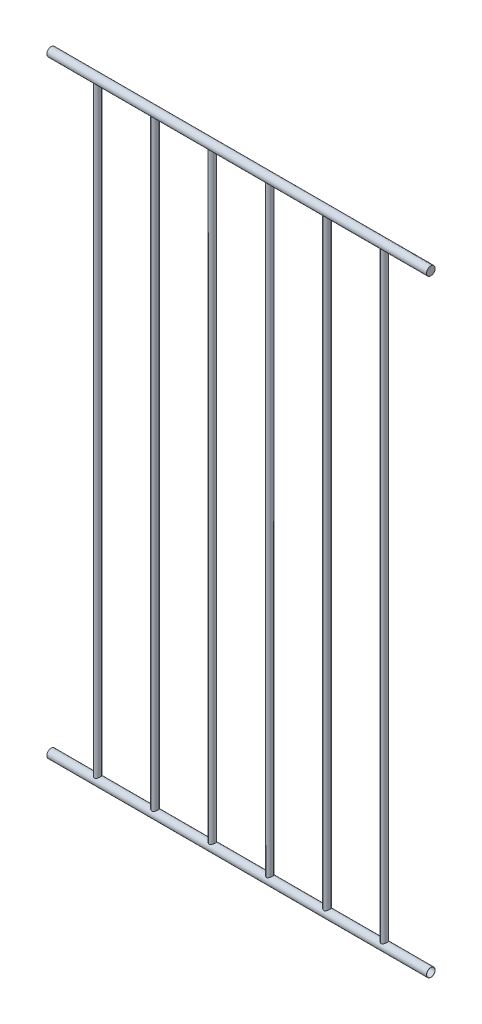
SolidWorks part; units mm, degrees
material "Copper"
ref_plane "Front Plane" through (0, 0, 0) normal (0, 0, 1) x (1, 0, 0)
ref_plane "Top Plane" through (0, 0, 0) normal (0, 1, 0) x (1, 0, 0)
ref_plane "Right Plane" through (0, 0, 0) normal (1, 0, 0) x (0, 0, -1)
sketch "Sketch1" plane through (0, 0, 0) normal (0, 0, 1) x (1, 0, 0)
  line L0 (0, 0) -> (1000, 0)
  line L1 (0, -1600) -> (1000, -1600)
  line L2 (122.5, 0) -> (122.5, -1600)
  line L3 (273.5, 0) -> (273.5, -1600)
  line L4 (424.5, 0) -> (424.5, -1600)
  line L5 (575.5, 0) -> (575.5, -1600)
  line L6 (726.5, 0) -> (726.5, -1600)
  line L7 (877.5, 0) -> (877.5, -1600)
  dimension "D1" = 1000
  dimension "D2" = 1000
  dimension "D3" = 1600
  dimension "D4" = 122.5
  dimension "D5" = 6
sketch "Sketch2" plane through (0, 0, 0) normal (1, 0, 0) x (0, 0, -1)
  line L0 (0, 0) -> (0, -1600) construction
  circle A0 centre (0, 0) radius 11.45
  circle A1 centre (0, -1600.0125) radius 11.45
  dimension "D1" = 22.9
  dimension "D3" = 22.9
extrude "Boss-Extrude1" add sketch "Sketch2" along normal blind 1000
sketch "Sketch3" plane through (0, 0, 0) normal (1, 0, 0) x (0, 0, -1)
  line L0 (0, 0) -> (0, -1600) construction
  circle A0 centre (0, 0) radius 11
  circle A1 centre (0, -1600) radius 11
  dimension "D1" = 22
  dimension "D2" = 22
extrude "Cut-Extrude1" cut sketch "Sketch3" along normal blind 1000
sketch "Sketch5" plane through (0, 0, 0) normal (0, 0, 1) x (1, 0, 0)
  line L0 (122.5, -800) -> (877.5, -800) construction
  line L1 (122.5, 0) -> (122.5, -1600) construction
  line L2 (877.5, 0) -> (877.5, -1600) construction
ref_plane "Plane2" through (0, -800, 0) normal (0, -1, 0) x (-1, 0, 0)
sketch "Sketch6" plane through (0, -800, 0) normal (0, -1, 0) x (-1, 0, 0)
  line L0 (0, 0) -> (-1000, 0) construction
  line L1 (-1000, 11.45) -> (-1000, -11.45) construction
  circle A0 centre (-122.5, 0) radius 8.0721
  circle A2 centre (-273.5, 0) radius 8.0721
  circle A3 centre (-424.5, 0) radius 8.0721
  circle A4 centre (-575.5, 0) radius 8.0721
  circle A5 centre (-726.5, 0) radius 8.0721
  circle A6 centre (-877.5, 0) radius 8.0721
  point P4 (-1000, 0)
  dimension "D1" = 122.5
  dimension "D2" = 122.5
extrude "Boss-Extrude3" add sketch "Sketch6" along normal up to surface and the other way up to surface up to face at (1000, -1600.0125, -11.45) other way up to face at (1000, 0, -11.45)
sketch "Sketch7" plane through (0, -800, 0) normal (0, -1, 0) x (-1, 0, 0)
  line L0 (0, 0) -> (-1000, 0) construction
  circle A0 centre (-122.5, 0) radius 7.5
  circle A1 centre (-273.5, 0) radius 7.5
  circle A2 centre (-424.5, 0) radius 7.5
  circle A3 centre (-575.5, 0) radius 7.5
  circle A4 centre (-726.5, 0) radius 7.5
  circle A5 centre (-877.5, 0) radius 7.5
  dimension "D1" = 15
  dimension "D2" = 122.5
extrude "Boss-Extrude4" add sketch "Sketch7" along normal up to surface and the other way up to surface up to face at (0, -1600.0125, -11.45) other way up to face at (1000, 0, -11.45)
sketch "Sketch8" plane through (0, 0, 0) normal (1, 0, 0) x (0, 0, -1)
  line L0 (0, 0) -> (0, -1600) construction
  circle A0 centre (0, -1600) radius 11
  circle A1 centre (0, 0) radius 11
extrude "Cut-Extrude2" cut sketch "Sketch8" along normal through all
sketch "Sketch9" plane through (0, -800, 0) normal (0, -1, 0) x (-1, 0, 0)
  line L0 (0, 0) -> (-1000, 0) construction
  line L1 (-1000, 11.45) -> (-1000, -11.45) construction
  circle A0 centre (-122.5, 0) radius 7.5
  circle A1 centre (-273.5, 0) radius 7.5
  circle A2 centre (-424.5, 0) radius 7.5
  circle A3 centre (-575.5, 0) radius 7.5
  circle A4 centre (-726.5, 0) radius 7.5
  circle A5 centre (-877.5, 0) radius 7.5
  dimension "D1" = 15
  dimension "D2" = 122.5
  dimension "D3" = 122.5
extrude "Cut-Extrude4" cut sketch "Sketch9" against normal up to next and the other way up to next
sketch "Sketch10" plane through (1000, 0, 0) normal (1, 0, 0) x (0, 0, -1)
  circle A0 centre (0, 0) radius 11
extrude "Boss-Extrude5" add sketch "Sketch10" against normal blind 2 separate body
sketch "Sketch11" plane through (0, 0, 0) normal (-1, 0, 0) x (0, 0, 1)
  circle A0 centre (0, -1600) radius 11
extrude "Boss-Extrude6" add sketch "Sketch11" against normal blind 2 separate body
